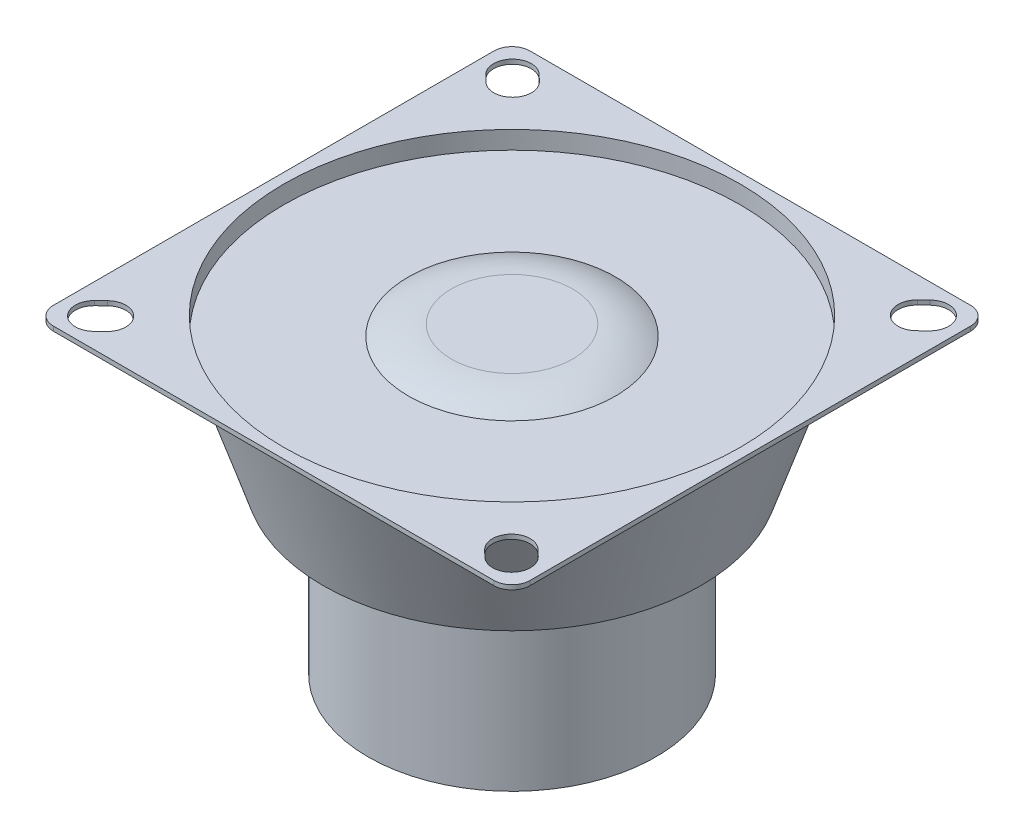
SolidWorks part; units mm, degrees
ref_plane "Plan de face" through (0, 0, 0) normal (0, 0, 1) x (1, 0, 0)
ref_plane "Plan de dessus" through (0, 0, 0) normal (0, 1, 0) x (1, 0, 0)
ref_plane "Plan de droite" through (0, 0, 0) normal (1, 0, 0) x (0, 0, -1)
sketch "Esquisse2" plane through (0, 0, 0) normal (0, 1, 0) x (1, 0, 0)
  circle A0 centre (0, 0) radius 16
  dimension "D1" = 32
extrude "Boss.-Extru.1" add sketch "Esquisse2" along normal blind 19
sketch "Esquisse3" plane through (0, 19, 0) normal (0, 1, 0) x (1, 0, 0)
  circle A0 centre (0, 0) radius 21
  dimension "D1" = 42
extrude "Boss.-Extru.2" add sketch "Esquisse3" along normal blind 15
draft "Dépouille1" type of draft neutral plane draft angle 18.5 faces to draft 1 face at (0, 34, 21) neutral plane through (0, 19, 0) neutral plane normal (0, -1, 0) parameters "D1"=18.5
sketch "Esquisse4" plane through (0, 34, 0) normal (0, 1, 0) x (1, 0, 0)
  line L0 (-26.0189, 0) -> (-26.5, 0) construction
  line L1 (-24.5, 26.5) -> (24.5, 26.5)
  line L2 (-26.5, 24.5) -> (-26.5, -24.5)
  line L3 (-24.5, -26.5) -> (24.5, -26.5)
  line L4 (26.5, 24.5) -> (26.5, -24.5)
  line L5 (26.0189, 0) -> (26.5, 0) construction
  line L6 (0, 26.0189) -> (0, 26.5) construction
  line L7 (0, -26.0189) -> (0, -26.5) construction
  circle A2 centre (0, 0) radius 26.0189 construction
  arc A3 (-26.5, -24.5) -> (-24.5, -26.5) centre (-24.5, -24.5) ccw
  arc A4 (24.5, -26.5) -> (26.5, -24.5) centre (24.5, -24.5) ccw
  arc A5 (24.5, 26.5) -> (26.5, 24.5) centre (24.5, 24.5) cw
  arc A6 (-24.5, 26.5) -> (-26.5, 24.5) centre (-24.5, 24.5) ccw
  point P19 (26.5, -26.5)
  point P22 (26.5, 26.5)
  point P25 (-26.5, 26.5)
  dimension "D3" = 2
  dimension "D1" = 53
  dimension "D2" = 53
extrude "Boss.-Extru.3" add sketch "Esquisse4" along normal blind 0.5
sketch "Esquisse5" plane through (0, 34.5, 0) normal (0, 1, 0) x (1, 0, 0)
  circle A0 centre (0, 0) radius 25.375
  dimension "D1" = 50.75
extrude "Enlèv. mat.-Extru.1" cut sketch "Esquisse5" against normal blind 2
sketch "Esquisse6" plane through (0, 32.5, 0) normal (0, 1, 0) x (1, 0, 0)
  circle A0 centre (0, 0) radius 11.5
  dimension "D1" = 23
extrude "Boss.-Extru.4" add sketch "Esquisse6" along normal blind 1.2
fillet "Congé1" radius 10 1 edges at (0, 33.7, 11.5)
sketch "Esquisse7" plane through (0, 34.5, 0) normal (0, 1, 0) x (1, 0, 0)
  line L0 (22.4843, 22.5565) -> (23.203, 23.2518) construction
  line L1 (21.024, 24.0656) -> (21.7427, 24.761)
  line L2 (23.9446, 21.0473) -> (24.6633, 21.7427)
  line L3 (24.7121, 24.7121) -> (25.9142, 25.9142) construction
  line L4 (24.5, 26.5) -> (-24.5, 26.5) construction
  line L5 (0, 26.5) -> (0, 19.7744) construction
  line L6 (26.5, 0) -> (19.3276, 0) construction
  line L7 (26.5, -24.5) -> (26.5, 24.5) construction
  line L8 (-22.4843, 22.5565) -> (-23.203, 23.2518) construction
  line L9 (-21.024, 24.0656) -> (-21.7427, 24.761)
  line L10 (-23.9446, 21.0473) -> (-24.6633, 21.7427)
  line L11 (22.4843, -22.5565) -> (23.203, -23.2518) construction
  line L12 (21.024, -24.0656) -> (21.7427, -24.761)
  line L13 (23.9446, -21.0473) -> (24.6633, -21.7427)
  line L14 (-22.4843, -22.5565) -> (-23.203, -23.2518) construction
  line L15 (-21.024, -24.0656) -> (-21.7427, -24.761)
  line L16 (-23.9446, -21.0473) -> (-24.6633, -21.7427)
  arc A0 (21.024, 24.0656) -> (23.9446, 21.0473) centre (22.4843, 22.5565) ccw
  arc A1 (24.6633, 21.7427) -> (21.7427, 24.761) centre (23.203, 23.2518) ccw
  arc A2 (26.5, 24.5) -> (24.5, 26.5) centre (24.5, 24.5) ccw construction
  arc A3 (-21.024, 24.0656) -> (-23.9446, 21.0473) centre (-22.4843, 22.5565) cw
  arc A4 (-24.6633, 21.7427) -> (-21.7427, 24.761) centre (-23.203, 23.2518) cw
  arc A5 (21.024, -24.0656) -> (23.9446, -21.0473) centre (22.4843, -22.5565) cw
  arc A6 (24.6633, -21.7427) -> (21.7427, -24.761) centre (23.203, -23.2518) cw
  arc A7 (-21.024, -24.0656) -> (-23.9446, -21.0473) centre (-22.4843, -22.5565) ccw
  arc A8 (-24.6633, -21.7427) -> (-21.7427, -24.761) centre (-23.203, -23.2518) ccw
  circle A9 centre (0, 0) radius 25.375 construction
  point P2 (22.8437, 22.9042)
  point P7 (20.9752, 21.0962)
  point P8 (24.7121, 24.7121)
  point P25 (-22.8437, 22.9042)
  point P32 (22.8437, -22.9042)
  point P39 (-22.8437, -22.9042)
  point P44 (-20.9752, 21.0962)
  dimension "D3" = 29.7491
  dimension "D1" = 5.2
  dimension "D2" = 4.2
  dimension "D4" = 45
  dimension "D5" = 1.7
extrude "Enlèv. mat.-Extru.2" cut sketch "Esquisse7" against normal blind 10
